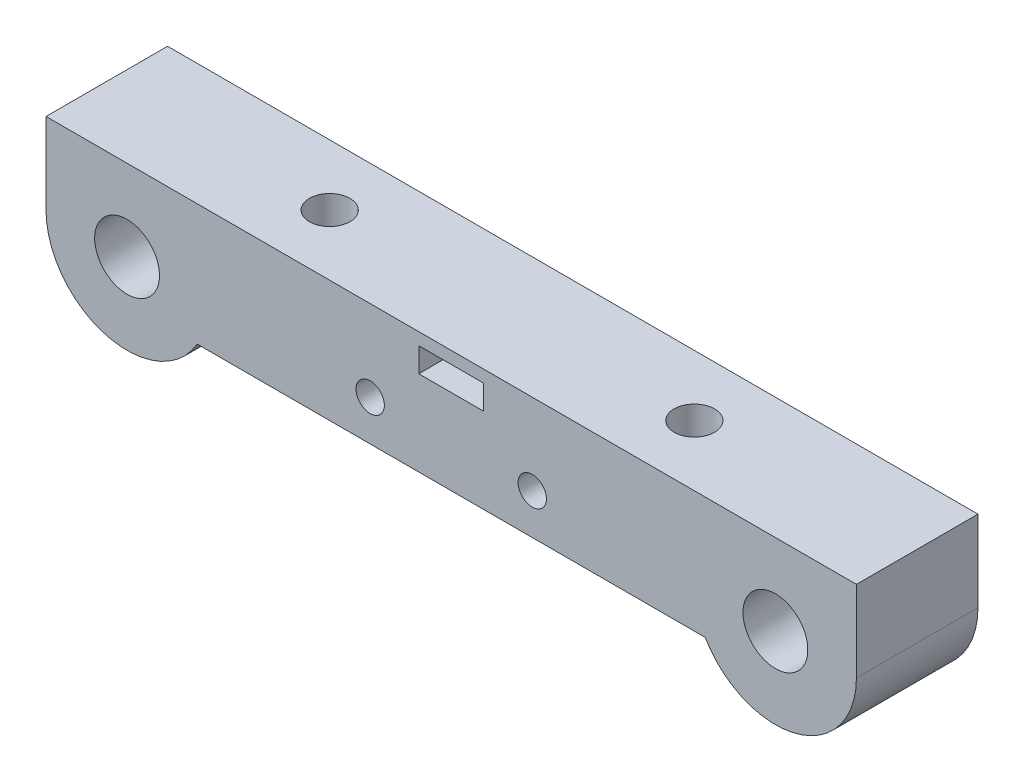
SolidWorks part; units mm, degrees
material "ABS"
ref_plane "Plano frontal" through (0, 0, 0) normal (0, 0, 1) x (1, 0, 0)
ref_plane "Plano superior" through (0, 0, 0) normal (0, 1, 0) x (1, 0, 0)
ref_plane "Plano direito" through (0, 0, 0) normal (1, 0, 0) x (0, 0, -1)
sketch "Esboço1" plane through (0, 0, 0) normal (0, 0, 1) x (1, 0, 0)
  line L0 (0, 0) -> (0, -15) construction
  line L1 (50, 0) -> (50, -10)
  line L2 (-50, -10) -> (-50, 0)
  line L3 (-50, 0) -> (50, 0)
  line L4 (10, -10) -> (-10, -10) construction
  line L5 (4, -1.5) -> (-4, -1.5)
  line L6 (4, -1.5) -> (4, -4.5)
  line L7 (-31.3397, -15) -> (31.3397, -15)
  line L8 (4, -4.5) -> (-4, -4.5)
  line L9 (-4, -1.5) -> (-4, -4.5)
  line L10 (4, -1.5) -> (-4, -4.5) construction
  line L11 (4, -4.5) -> (-4, -1.5) construction
  circle A0 centre (-40, -10) radius 4
  circle A1 centre (40, -10) radius 4
  arc A2 (-50, -10) -> (-31.3397, -15) centre (-40, -10) ccw
  arc A3 (50, -10) -> (31.3397, -15) centre (40, -10) cw
  circle A4 centre (10, -10) radius 1.75
  circle A5 centre (-10, -10) radius 1.75
  point P0 (0, 0)
  point P2 (0, -3)
  point P13 (63, -13)
  point P24 (0, -10)
  point P25 (0, -15)
  dimension "D3" = 8
  dimension "D4" = 80
  dimension "D2" = 10
  dimension "D8" = 3.5
  dimension "D1" = 100
  dimension "D5" = 3
  dimension "D6" = 8
  dimension "D7" = 3
  dimension "D9" = 20
  dimension "D10" = 15
  dimension "D11" = 5
extrude "Ressalto-extrusão1" add sketch "Esboço1" along normal blind 15
sketch "Esboço2" plane through (0, -15, 0) normal (0, -1, 0) x (1, 0, 0)
  line L0 (0, 0) -> (0, 15) construction
  line L1 (-31.3397, 0) -> (31.3397, 0) construction
  line L2 (-31.3397, 15) -> (31.3397, 15) construction
  circle A0 centre (-22.5, 7.5) radius 2.5
  circle A1 centre (22.5, 7.5) radius 2.5
  point P11 (0, 7.5)
  dimension "D2" = 5
  dimension "D1" = 45
extrude "Corte-extrusão1" cut sketch "Esboço2" against normal blind 15 contours A1 | A0 region at (22.5, -15, 7.5)
